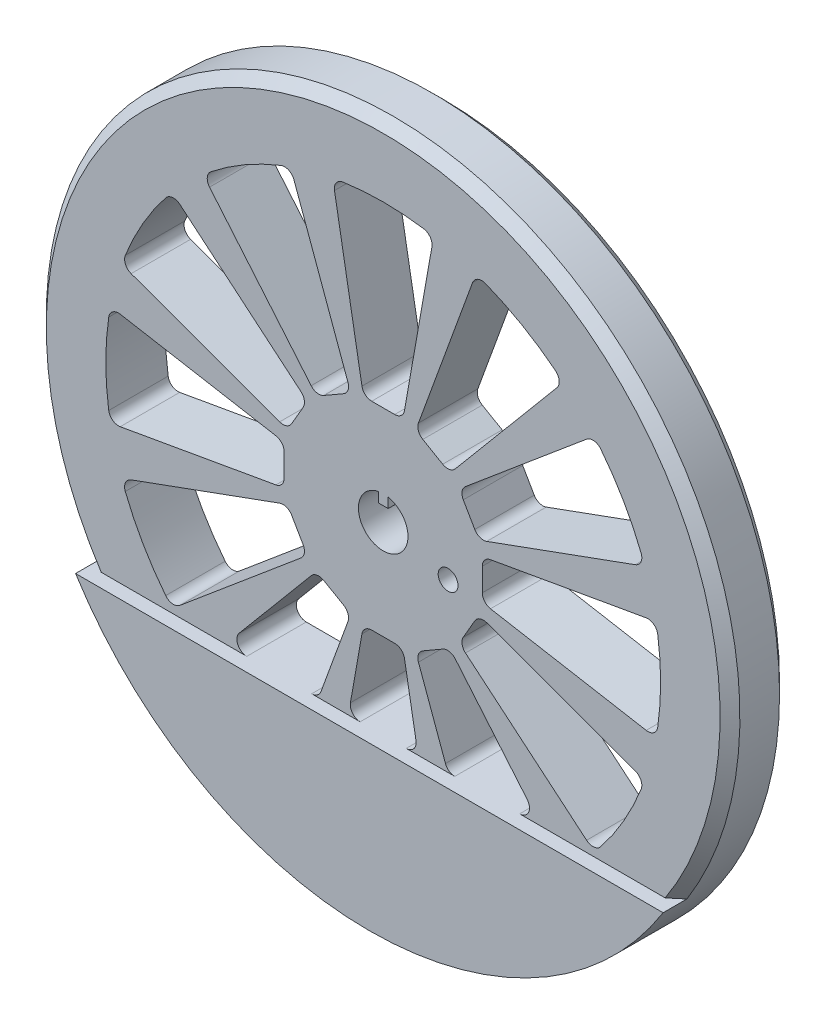
SolidWorks part; units mm, degrees
material "6061 Alloy"
ref_plane "Front Plane" through (0, 0, 0) normal (0, 0, 1) x (1, 0, 0)
ref_plane "Top Plane" through (0, 0, 0) normal (0, 1, 0) x (1, 0, 0)
ref_plane "Right Plane" through (0, 0, 0) normal (1, 0, 0) x (0, 0, -1)
sketch "Sketch2" plane through (0, 0, 0) normal (0, 0, 1) x (1, 0, 0)
  line L0 (0, 0) -> (0, 50) construction
  line L1 (-10, 50) -> (10, 50)
  line L2 (-10, 50) -> (-25.4579, 137.6659)
  line L3 (10, 50) -> (25.4579, 137.6659)
  line L4 (16.3397, 48.3013) -> (46.7858, 131.9511)
  line L5 (33.6603, 38.3013) -> (90.8801, 106.4932)
  line L6 (16.3397, 48.3013) -> (33.6603, 38.3013)
  line L7 (38.3013, 33.6603) -> (106.4932, 90.8801)
  line L8 (48.3013, 16.3397) -> (131.9511, 46.7858)
  line L9 (38.3013, 33.6603) -> (48.3013, 16.3397)
  line L10 (50, 10) -> (137.6659, 25.4579)
  line L11 (50, -10) -> (137.6659, -25.4579)
  line L12 (50, 10) -> (50, -10)
  line L13 (48.3013, -16.3397) -> (131.9511, -46.7858)
  line L14 (38.3013, -33.6603) -> (106.4932, -90.8801)
  line L15 (48.3013, -16.3397) -> (38.3013, -33.6603)
  line L16 (33.6603, -38.3013) -> (90.8801, -106.4932)
  line L17 (16.3397, -48.3013) -> (46.7858, -131.9511)
  line L18 (33.6603, -38.3013) -> (16.3397, -48.3013)
  line L19 (10, -50) -> (25.4579, -137.6659)
  line L20 (-10, -50) -> (-25.4579, -137.6659)
  line L21 (10, -50) -> (-10, -50)
  line L22 (-16.3397, -48.3013) -> (-46.7858, -131.9511)
  line L23 (-33.6603, -38.3013) -> (-90.8801, -106.4932)
  line L24 (-16.3397, -48.3013) -> (-33.6603, -38.3013)
  line L25 (-38.3013, -33.6603) -> (-106.4932, -90.8801)
  line L26 (-48.3013, -16.3397) -> (-131.9511, -46.7858)
  line L27 (-38.3013, -33.6603) -> (-48.3013, -16.3397)
  line L28 (-50, -10) -> (-137.6659, -25.4579)
  line L29 (-50, 10) -> (-137.6659, 25.4579)
  line L30 (-50, -10) -> (-50, 10)
  line L31 (-48.3013, 16.3397) -> (-131.9511, 46.7858)
  line L32 (-38.3013, 33.6603) -> (-106.4932, 90.8801)
  line L33 (-48.3013, 16.3397) -> (-38.3013, 33.6603)
  line L34 (-33.6603, 38.3013) -> (-90.8801, 106.4932)
  line L35 (-16.3397, 48.3013) -> (-46.7858, 131.9511)
  line L36 (-33.6603, 38.3013) -> (-16.3397, 48.3013)
  line L37 (0, 155) -> (0, 140) construction
  line L38 (0, 0) -> (32.739, -8.7724) construction
  line L39 (0, 0) -> (0, -28.4859) construction
  line L40 (2.5, 12.5) -> (-2.5, 12.5) construction
  line L42 (-2.5, 7.2474) -> (2.5, 7.2474)
  line L44 (-2.5, 12.2474) -> (-2.5, 7.2474)
  line L45 (2.5, 7.2474) -> (2.5, 12.2474)
  line L46 (-148.243, -93) -> (148.243, -93)
  line L47 (0, -93) -> (0, -175) construction
  circle A0 centre (0, 0) radius 175
  circle A1 centre (0, 0) radius 12.5
  arc A2 (-25.4579, 137.6659) -> (25.4579, 137.6659) centre (0, 0) cw
  arc A3 (46.7858, 131.9511) -> (90.8801, 106.4932) centre (0, 0) cw
  arc A4 (106.4932, 90.8801) -> (131.9511, 46.7858) centre (0, 0) cw
  arc A5 (137.6659, 25.4579) -> (137.6659, -25.4579) centre (0, 0) cw
  arc A6 (131.9511, -46.7858) -> (106.4932, -90.8801) centre (0, 0) cw
  arc A7 (90.8801, -106.4932) -> (46.7858, -131.9511) centre (0, 0) cw
  arc A8 (25.4579, -137.6659) -> (-25.4579, -137.6659) centre (0, 0) cw
  arc A9 (-46.7858, -131.9511) -> (-90.8801, -106.4932) centre (0, 0) cw
  arc A10 (-106.4932, -90.8801) -> (-131.9511, -46.7858) centre (0, 0) cw
  arc A11 (-137.6659, -25.4579) -> (-137.6659, 25.4579) centre (0, 0) cw
  arc A12 (-131.9511, 46.7858) -> (-106.4932, 90.8801) centre (0, 0) cw
  arc A13 (-90.8801, 106.4932) -> (-46.7858, 131.9511) centre (0, 0) cw
  circle A14 centre (0, 155) radius 5
  circle A17 centre (32.739, -8.7724) radius 5
  point P7 (0, 50)
  point P36 (0, 0)
  point P39 (0, 0)
  point P40 (0, 0)
  point P46 (0, 12.5)
  point P56 (0, 0)
  point P73 (0, 0)
  dimension "D1" = 350
  dimension "D4" = 10
  dimension "D6" = 15
  dimension "D7" = 10
  dimension "D10" = 75
  dimension "D9" = 35
  dimension "D11" = 5
  dimension "D12" = 5
  dimension "D2" = 50
  dimension "D3" = 20
  dimension "D5" = 10
  dimension "D13" = 5
  dimension "D14" = 82
  dimension "D8" = 12
extrude "Boss-Extrude1" add sketch "Sketch2" along normal mid plane 30 contours A0 A17 A14 A1 L2 A2 L3 L1 L4 A3 L5 L6 L7 A4 L8 L9 L10 A5 L11 L12 L13 A6 L14 L15 L16 A7 L17 L18 L19 A8 L20 L21 L22 A9 L23 L24 L25 A10 | L45 A1 L44 L42 | A14 | L22 A9 L46 A0 A7 L17 L19 A8 L20 | A8 L19 L46 L20 | A9 L22 L46 | A7 L46 L17 region at (-0.0571, 35.8625, 0) region at (113.9005, -96.0762, 0) region at (59.8624, -108.1442, 0) region at (0, -117.5636, 0) region at (-59.8624, -108.1442, 0) region at (0, 9.8324, 0) region at (0, 155, 0)
chamfer "Chamfer1" distance 5 angle 45 2 edges at (175, 0, -15) (175, 0, 15) tangent propagation no
fillet "Fillet1" radius 5 24 edges at (10, 50, 0) (-10, 50, 0) (-33.6603, -38.3013, 0) (-16.3397, -48.3013, 0) (-10, -50, 0) (10, -50, 0) (16.3397, -48.3013, 0) (33.6603, -38.3013, 0) (38.3013, -33.6603, 0) (48.3013, -16.3397, 0) (50, -10, 0) (50, 10, 0) (48.3013, 16.3397, 0) (38.3013, 33.6603, 0) (33.6603, 38.3013, 0) (16.3397, 48.3013, 0) (-48.3013, -16.3397, 0) (-38.3013, 33.6603, 0) (-50, 10, 0) (-33.6603, 38.3013, 0) (-38.3013, -33.6603, 0) (-50, -10, 0) (-48.3013, 16.3397, 0) (-16.3397, 48.3013, 0)
fillet "Fillet2" radius 5 24 edges at (-46.7858, 131.9511, 0) (-90.8801, 106.4932, 0) (-106.4932, 90.8801, 0) (-131.9511, 46.7858, 0) (-137.6659, 25.4579, 0) (-137.6659, -25.4579, 0) (-131.9511, -46.7858, 0) (137.6659, 25.4579, 0) (106.4932, 90.8801, 0) (46.7858, 131.9511, 0) (131.9511, -46.7858, 0) (-106.4932, -90.8801, 0) (106.4932, -90.8801, 0) (137.6659, -25.4579, 0) (131.9511, 46.7858, 0) (90.8801, 106.4932, 0) (25.4579, 137.6659, 0) (-25.4579, 137.6659, 0) (-32.6088, -93, 0) (-17.5821, -93, 0) (17.5821, -93, 0) (32.6088, -93, 0) (-79.5579, -93, 0) (79.5579, -93, 0)
extrude "Boss-Extrude2" add sketch "Sketch2<3>" along normal blind 22 contours L22 A9 L23 L46 A0 L16 A7 L17 L19 A8 L20 | A9 L22 L46 L23 | A8 L19 L46 L20 | A7 L16 L46 L17 region at (113.9005, -96.0762, 0) region at (59.8624, -108.1442, 0) region at (0, -117.5636, 0) region at (-59.8624, -108.1442, 0)
sketch "Sketch2<3>" plane through (0, 0, 0) normal (0, 0, 1) x (1, 0, 0) same geometry as "Sketch2"
